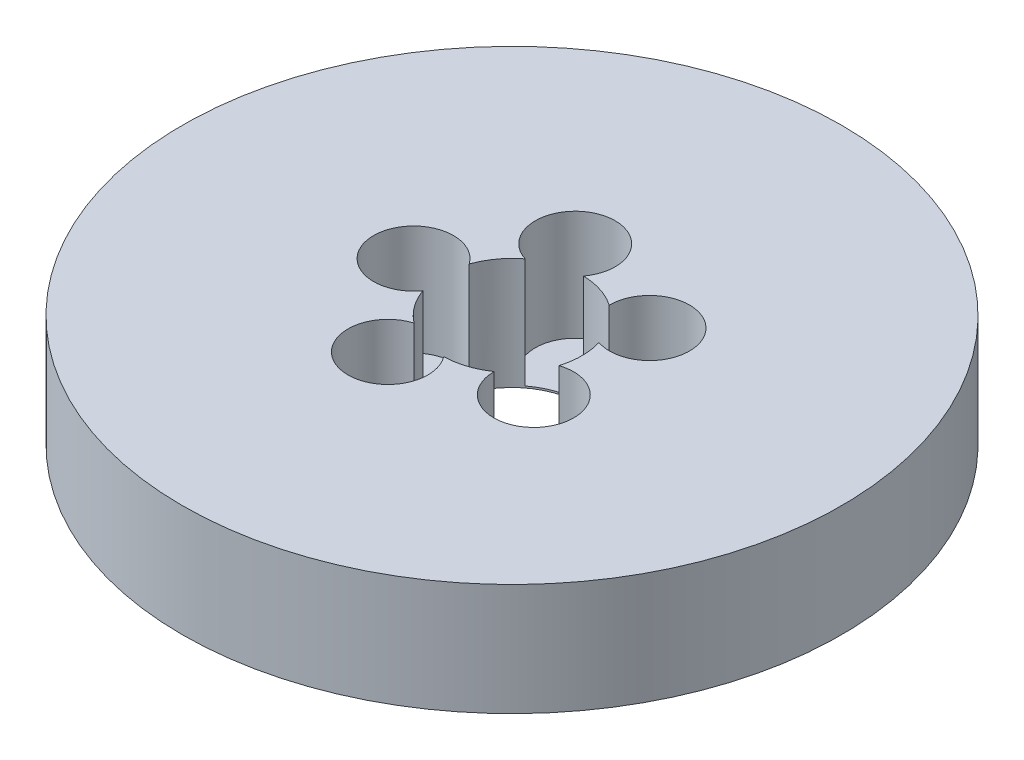
SolidWorks part; units mm, degrees
ref_plane "Front Plane" through (0, 0, 0) normal (0, 0, 1) x (1, 0, 0)
ref_plane "Top Plane" through (0, 0, 0) normal (0, 1, 0) x (1, 0, 0)
ref_plane "Right Plane" through (0, 0, 0) normal (1, 0, 0) x (0, 0, -1)
sketch "Sketch1" plane through (0, 0, 0) normal (0, 1, 0) x (1, 0, 0)
  circle A0 centre (0, 0) radius 82.5
  dimension "FLANGE_OD" = 165
extrude "Boss-Extrude1" add sketch "Sketch1" along normal blind 28
sketch "Sketch2" plane through (0, 0, 0) normal (0, 1, 0) x (1, 0, 0)
  circle A0 centre (0, 0) radius 17.5
  dimension "BORE_D" = 35
extrude "Cut-Extrude1" cut sketch "Sketch2" along normal through all
sketch "Sketch3" plane through (0, 28, 0) normal (0, 1, 0) x (1, 0, 0)
  circle A0 centre (0, 0) radius 24.6513 construction
  circle A1 centre (-24.6513, 0) radius 10
  dimension "BOLT_D" = 20
  dimension "BOLT_PCD" = 49.3026
extrude "Cut-Extrude2" cut sketch "Sketch3" against normal blind 27.5477
pattern_circular "CirPattern1" count 5 over 360 about axis through (0, 0, 0) along (0, 1, 0) of "Cut-Extrude2"
